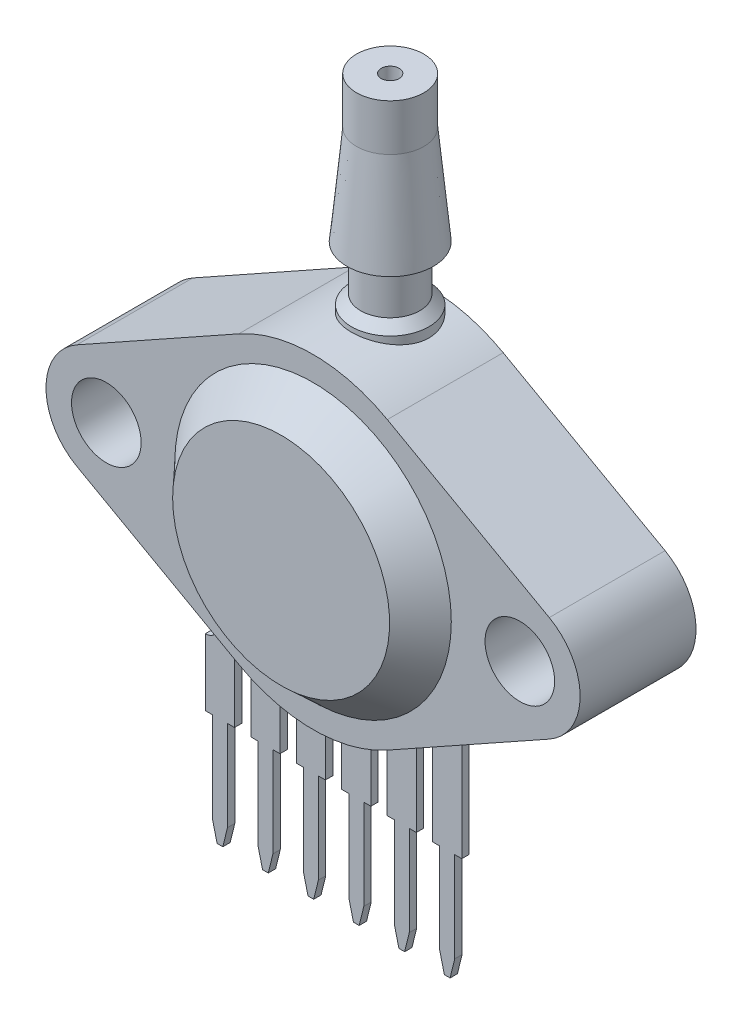
SolidWorks part; units mm, degrees
ref_plane "Front Plane" through (0, 0, 0) normal (0, 0, 1) x (1, 0, 0)
ref_plane "Top Plane" through (0, 0, 0) normal (0, 1, 0) x (1, 0, 0)
ref_plane "Right Plane" through (0, 0, 0) normal (1, 0, 0) x (0, 0, -1)
sketch "Sketch1" plane through (0, 0, 0) normal (0, 0, 1) x (1, 0, 0)
  line L0 (-7.165, -6.4913) -> (-7.165, -7.1728)
  line L1 (-4.625, -8.5934) -> (-4.625, -12.32)
  line L2 (-2.995, -12.32) -> (-2.995, -8.5831)
  line L3 (-7.165, -8.5934) -> (-7.165, -12.32)
  line L4 (-7.165, -12.32) -> (-6.77, -12.32)
  line L5 (-6.77, -12.32) -> (-6.77, -17.3607)
  line L6 (-6.77, -17.3607) -> (-6.5103, -18.42)
  line L7 (-6.5103, -18.42) -> (-6.1897, -18.42)
  line L8 (-6.1897, -18.42) -> (-5.93, -17.3607)
  line L9 (-5.93, -17.3607) -> (-5.93, -12.32)
  line L10 (-5.93, -12.32) -> (-5.535, -12.32)
  line L11 (-5.535, -12.32) -> (-5.535, -8.5831)
  line L12 (-3.39, -12.32) -> (-2.995, -12.32)
  line L13 (-3.39, -17.3607) -> (-3.39, -12.32)
  line L14 (-4.23, -12.32) -> (-4.23, -17.3607)
  line L15 (-4.625, -12.32) -> (-4.23, -12.32)
  line L16 (-3.6497, -18.42) -> (-3.39, -17.3607)
  line L17 (-4.23, -17.3607) -> (-3.9703, -18.42)
  line L18 (-3.9703, -18.42) -> (-3.6497, -18.42)
  line L19 (-2.085, -8.5934) -> (-2.085, -12.32)
  line L20 (-0.455, -12.32) -> (-0.455, -8.5831)
  line L21 (-0.85, -12.32) -> (-0.455, -12.32)
  line L22 (-0.85, -17.3607) -> (-0.85, -12.32)
  line L23 (-1.69, -12.32) -> (-1.69, -17.3607)
  line L24 (-2.085, -12.32) -> (-1.69, -12.32)
  line L25 (-1.1097, -18.42) -> (-0.85, -17.3607)
  line L26 (-1.69, -17.3607) -> (-1.4303, -18.42)
  line L27 (-1.4303, -18.42) -> (-1.1097, -18.42)
  line L28 (0.455, -8.5934) -> (0.455, -12.32)
  line L29 (2.085, -12.32) -> (2.085, -8.5831)
  line L30 (1.69, -12.32) -> (2.085, -12.32)
  line L31 (1.69, -17.3607) -> (1.69, -12.32)
  line L32 (0.85, -12.32) -> (0.85, -17.3607)
  line L33 (0.455, -12.32) -> (0.85, -12.32)
  line L34 (1.4303, -18.42) -> (1.69, -17.3607)
  line L35 (0.85, -17.3607) -> (1.1097, -18.42)
  line L36 (1.1097, -18.42) -> (1.4303, -18.42)
  line L37 (2.995, -8.5934) -> (2.995, -12.32)
  line L38 (4.625, -12.32) -> (4.625, -8.5831)
  line L39 (4.23, -12.32) -> (4.625, -12.32)
  line L40 (4.23, -17.3607) -> (4.23, -12.32)
  line L41 (3.39, -12.32) -> (3.39, -17.3607)
  line L42 (2.995, -12.32) -> (3.39, -12.32)
  line L43 (3.9703, -18.42) -> (4.23, -17.3607)
  line L44 (3.39, -17.3607) -> (3.6497, -18.42)
  line L45 (3.6497, -18.42) -> (3.9703, -18.42)
  line L46 (5.535, -8.5934) -> (5.535, -12.32)
  line L47 (7.165, -12.32) -> (7.165, -8.5831)
  line L48 (6.77, -12.32) -> (7.165, -12.32)
  line L49 (6.77, -17.3607) -> (6.77, -12.32)
  line L50 (5.93, -12.32) -> (5.93, -17.3607)
  line L51 (5.535, -12.32) -> (5.93, -12.32)
  line L52 (6.5103, -18.42) -> (6.77, -17.3607)
  line L53 (5.93, -17.3607) -> (6.1897, -18.42)
  line L54 (6.1897, -18.42) -> (6.5103, -18.42)
  line L55 (-7.165, -8.5934) -> (-4.625, -8.5934) construction
  line L56 (-6.35, -18.42) -> (-6.35, -17.3607) construction
  line L57 (-6.35, -17.3607) -> (-6.77, -17.3607) construction
  line L58 (-5.93, -17.3607) -> (-6.35, -17.3607) construction
  line L59 (0.455, -12.32) -> (0, -12.32) construction
  line L60 (0, -12.32) -> (-0.455, -12.32) construction
  line L61 (-13.1991, 2.9418) -> (-4.1499, 7.9991)
  line L62 (0, 0) -> (-11.555, 0) construction
  line L63 (4.1499, 7.9991) -> (13.1991, 2.9418)
  line L64 (0, 0) -> (0, 0.5736) construction
  line L65 (4.1499, -7.9991) -> (13.1991, -2.9418)
  line L66 (-13.1991, -2.9418) -> (-4.1499, -7.9991)
  arc A0 (-7.165, -7.1728) -> (-7.165, -8.5934) centre (-7.165, -7.8831) cw
  circle A1 centre (-11.555, 0) radius 1.945
  circle A2 centre (11.555, 0) radius 1.945
  arc A3 (-13.1991, 2.9418) -> (-13.1991, -2.9418) centre (-11.555, 0) ccw
  arc A4 (13.1991, -2.9418) -> (13.1991, 2.9418) centre (11.555, 0) ccw
  arc A5 (4.1499, 7.9991) -> (-4.1499, 7.9991) centre (0, 0.5736) ccw
  arc A6 (4.1499, -7.9991) -> (-4.1499, -7.9991) centre (0, -0.5736) cw
  dimension "D6" = 3.89
  dimension "D8" = 23.11
  dimension "D9" = 29.85
  dimension "D1" = 2.54
  dimension "D2" = 1.63
  dimension "D3" = 0.84
  dimension "D4" = 6.1
  dimension "D5" = 18.42
  dimension "D7" = 18.16
sketch "Sketch2" plane through (0, 0, 0) normal (1, 0, 0) x (0, 0, -1)
  line L0 (2.165, -9.08) -> (-2.7529, -9.08)
  line L1 (-4.3102, -9.08) -> (-4.3102, -7.725)
  line L2 (-4.3102, -7.725) -> (-6.095, -6.0632)
  line L3 (-6.095, -6.0632) -> (-6.095, 6.0632)
  line L4 (-6.095, 6.0632) -> (-3.5225, 9.08)
  line L5 (-3.5225, 9.08) -> (-2.165, 9.08)
  line L6 (-2.165, 9.08) -> (-2.165, 9.3423)
  line L7 (-2.165, 9.3423) -> (-1.649, 9.8579)
  line L8 (-1.649, 9.8579) -> (-1.649, 12.3871)
  line L9 (-1.649, 12.3871) -> (2.4115, 12.3871)
  line L10 (2.4115, 12.3871) -> (1.878, 17.9217)
  line L11 (1.878, 17.9217) -> (1.878, 20.5223)
  line L12 (1.878, 20.5223) -> (-1.878, 20.5223)
  line L13 (1.649, 12.3871) -> (-2.4115, 12.3871)
  line L14 (2.165, 9.3423) -> (1.649, 9.8579)
  line L15 (1.649, 9.8579) -> (1.649, 12.3871)
  line L16 (-2.4115, 12.3871) -> (-1.878, 17.9217)
  line L17 (-1.878, 17.9217) -> (-1.878, 20.5223)
  line L18 (-3.1629, -9.08) -> (-4.3102, -9.08)
  line L19 (2.165, 9.3423) -> (2.165, -9.08)
  line L20 (0, 0) -> (0, 20.5223) construction
  line L21 (0, 2.9418) -> (0, -2.9418) construction
  line L22 (-3.1629, -18.6959) -> (-2.7529, -18.6959)
  line L23 (-3.1629, -18.6959) -> (-3.1629, -9.08)
  line L25 (-2.7529, -18.6959) -> (-2.7529, -9.08)
  point P17 (-6.095, 0)
  point P28 (0, -9.08)
  point P30 (0, 9.08)
  dimension "D1" = 6.095
  dimension "D2" = 8.26
  dimension "D3" = 3.7561
  dimension "D4" = 11.18
  dimension "D5" = 18.16
  dimension "D6" = 0.41
sketch "Sketch7" plane through (0, 0, 0) normal (0, 0, 1) x (1, 0, 0)
  line L0 (-5.535, -12.32) -> (-5.535, -8.5831) construction
  line L1 (-5.93, -12.32) -> (-5.535, -12.32) construction
  line L2 (-5.93, -17.3607) -> (-5.93, -12.32) construction
  line L3 (-6.1897, -18.42) -> (-5.93, -17.3607) construction
  line L4 (-6.5103, -18.42) -> (-6.1897, -18.42) construction
  line L5 (-6.77, -17.3607) -> (-6.5103, -18.42) construction
  line L6 (-6.77, -12.32) -> (-6.77, -17.3607) construction
  line L7 (-7.165, -12.32) -> (-6.77, -12.32) construction
  line L8 (-7.165, -8.5934) -> (-7.165, -12.32) construction
  line L9 (-7.165, -6.4913) -> (-7.165, -7.1728) construction
  line L10 (-4.625, -8.5934) -> (-4.625, -12.32) construction
  line L11 (-4.625, -12.32) -> (-4.23, -12.32) construction
  line L12 (-4.23, -12.32) -> (-4.23, -17.3607) construction
  line L13 (-4.23, -17.3607) -> (-3.9703, -18.42) construction
  line L14 (-3.9703, -18.42) -> (-3.6497, -18.42) construction
  line L15 (-3.6497, -18.42) -> (-3.39, -17.3607) construction
  line L16 (-3.39, -17.3607) -> (-3.39, -12.32) construction
  line L17 (-3.39, -12.32) -> (-2.995, -12.32) construction
  line L18 (-2.995, -12.32) -> (-2.995, -8.5831) construction
  line L19 (-0.455, -12.32) -> (-0.455, -8.5831) construction
  line L20 (-0.85, -12.32) -> (-0.455, -12.32) construction
  line L21 (-0.85, -17.3607) -> (-0.85, -12.32) construction
  line L22 (-1.1097, -18.42) -> (-0.85, -17.3607) construction
  line L23 (-1.4303, -18.42) -> (-1.1097, -18.42) construction
  line L24 (-1.69, -17.3607) -> (-1.4303, -18.42) construction
  line L25 (-1.69, -12.32) -> (-1.69, -17.3607) construction
  line L26 (-2.085, -12.32) -> (-1.69, -12.32) construction
  line L27 (-2.085, -8.5934) -> (-2.085, -12.32) construction
  line L28 (4.625, -12.32) -> (4.625, -8.5831) construction
  line L29 (4.23, -12.32) -> (4.625, -12.32) construction
  line L30 (4.23, -17.3607) -> (4.23, -12.32) construction
  line L31 (3.9703, -18.42) -> (4.23, -17.3607) construction
  line L32 (3.6497, -18.42) -> (3.9703, -18.42) construction
  line L33 (3.39, -17.3607) -> (3.6497, -18.42) construction
  line L34 (3.39, -12.32) -> (3.39, -17.3607) construction
  line L35 (2.995, -12.32) -> (3.39, -12.32) construction
  line L36 (2.995, -8.5934) -> (2.995, -12.32) construction
  line L37 (0.455, -8.5934) -> (0.455, -12.32) construction
  line L38 (0.455, -12.32) -> (0.85, -12.32) construction
  line L39 (0.85, -12.32) -> (0.85, -17.3607) construction
  line L40 (0.85, -17.3607) -> (1.1097, -18.42) construction
  line L41 (1.1097, -18.42) -> (1.4303, -18.42) construction
  line L42 (1.4303, -18.42) -> (1.69, -17.3607) construction
  line L43 (1.69, -17.3607) -> (1.69, -12.32) construction
  line L44 (1.69, -12.32) -> (2.085, -12.32) construction
  line L45 (2.085, -12.32) -> (2.085, -8.5831) construction
  line L46 (5.535, -8.5934) -> (5.535, -12.32) construction
  line L47 (5.535, -12.32) -> (5.93, -12.32) construction
  line L48 (5.93, -12.32) -> (5.93, -17.3607) construction
  line L49 (5.93, -17.3607) -> (6.1897, -18.42) construction
  line L50 (6.1897, -18.42) -> (6.5103, -18.42) construction
  line L51 (6.5103, -18.42) -> (6.77, -17.3607) construction
  line L52 (6.77, -17.3607) -> (6.77, -12.32) construction
  line L53 (6.77, -12.32) -> (7.165, -12.32) construction
  line L54 (7.165, -12.32) -> (7.165, -8.5831) construction
  line L55 (-5.535, -12.32) -> (-5.535, -7.225)
  line L56 (-5.93, -12.32) -> (-5.535, -12.32)
  line L57 (-5.93, -17.3607) -> (-5.93, -12.32)
  line L58 (-6.1897, -18.42) -> (-5.93, -17.3607)
  line L59 (-6.5103, -18.42) -> (-6.1897, -18.42)
  line L60 (-6.77, -17.3607) -> (-6.5103, -18.42)
  line L61 (-6.77, -12.32) -> (-6.77, -17.3607)
  line L62 (-7.165, -12.32) -> (-6.77, -12.32)
  line L63 (-7.165, -8.5934) -> (-7.165, -12.32)
  line L64 (-7.165, -6.314) -> (-7.165, -7.1728)
  line L65 (-4.625, -7.7335) -> (-4.625, -12.32)
  line L66 (-4.625, -12.32) -> (-4.23, -12.32)
  line L67 (-4.23, -12.32) -> (-4.23, -17.3607)
  line L68 (-4.23, -17.3607) -> (-3.9703, -18.42)
  line L69 (-3.9703, -18.42) -> (-3.6497, -18.42)
  line L70 (-3.6497, -18.42) -> (-3.39, -17.3607)
  line L71 (-3.39, -17.3607) -> (-3.39, -12.32)
  line L72 (-3.39, -12.32) -> (-2.995, -12.32)
  line L73 (-2.995, -12.32) -> (-2.995, -8.5353)
  line L74 (-0.455, -12.32) -> (-0.455, -9.0678)
  line L75 (-0.85, -12.32) -> (-0.455, -12.32)
  line L76 (-0.85, -17.3607) -> (-0.85, -12.32)
  line L77 (-1.1097, -18.42) -> (-0.85, -17.3607)
  line L78 (-1.4303, -18.42) -> (-1.1097, -18.42)
  line L79 (-1.69, -17.3607) -> (-1.4303, -18.42)
  line L80 (-1.69, -12.32) -> (-1.69, -17.3607)
  line L81 (-2.085, -12.32) -> (-1.69, -12.32)
  line L82 (-2.085, -8.8205) -> (-2.085, -12.32)
  line L83 (4.625, -12.32) -> (4.625, -7.7335)
  line L84 (4.23, -12.32) -> (4.625, -12.32)
  line L85 (4.23, -17.3607) -> (4.23, -12.32)
  line L86 (3.9703, -18.42) -> (4.23, -17.3607)
  line L87 (3.6497, -18.42) -> (3.9703, -18.42)
  line L88 (3.39, -17.3607) -> (3.6497, -18.42)
  line L89 (3.39, -12.32) -> (3.39, -17.3607)
  line L90 (2.995, -12.32) -> (3.39, -12.32)
  line L91 (2.995, -8.5353) -> (2.995, -12.32)
  line L92 (0.455, -9.0678) -> (0.455, -12.32)
  line L93 (0.455, -12.32) -> (0.85, -12.32)
  line L94 (0.85, -12.32) -> (0.85, -17.3607)
  line L95 (0.85, -17.3607) -> (1.1097, -18.42)
  line L96 (1.1097, -18.42) -> (1.4303, -18.42)
  line L97 (1.4303, -18.42) -> (1.69, -17.3607)
  line L98 (1.69, -17.3607) -> (1.69, -12.32)
  line L99 (1.69, -12.32) -> (2.085, -12.32)
  line L100 (2.085, -12.32) -> (2.085, -8.8205)
  line L101 (5.535, -7.225) -> (5.535, -12.32)
  line L102 (5.535, -12.32) -> (5.93, -12.32)
  line L103 (5.93, -12.32) -> (5.93, -17.3607)
  line L104 (5.93, -17.3607) -> (6.1897, -18.42)
  line L105 (6.1897, -18.42) -> (6.5103, -18.42)
  line L106 (6.5103, -18.42) -> (6.77, -17.3607)
  line L107 (6.77, -17.3607) -> (6.77, -12.32)
  line L108 (6.77, -12.32) -> (7.165, -12.32)
  line L109 (7.165, -12.32) -> (7.165, -6.314)
  line L110 (5.535, -7.225) -> (7.165, -6.314)
  line L111 (-4.625, -7.7335) -> (-4.1499, -7.9991)
  line L114 (4.1499, -7.9991) -> (13.1991, -2.9418)
  line L115 (-13.1991, -2.9418) -> (-4.1499, -7.9991)
  line L116 (-4.1499, 7.9991) -> (-13.1991, 2.9418)
  line L117 (13.1991, 2.9418) -> (4.1499, 7.9991)
  line L118 (4.1499, -7.9991) -> (4.625, -7.7335)
  line L119 (-7.165, -6.314) -> (-5.535, -7.225)
  arc A0 (-7.165, -8.5934) -> (-7.165, -7.1728) centre (-7.165, -7.8831) ccw construction
  arc A1 (-7.165, -8.5934) -> (-7.165, -7.1728) centre (-7.165, -7.8831) ccw
  arc A2 (2.995, -8.5353) -> (4.1499, -7.9991) centre (0, -0.5736) ccw
  arc A3 (0.455, -9.0678) -> (2.085, -8.8205) centre (0, -0.5736) ccw
  arc A4 (-2.085, -8.8205) -> (-0.455, -9.0678) centre (0, -0.5736) ccw
  arc A10 (13.1991, -2.9418) -> (13.1991, 2.9418) centre (11.555, 0) ccw
  arc A11 (-4.1499, -7.9991) -> (4.1499, -7.9991) centre (0, -0.5736) ccw
  arc A12 (-13.1991, 2.9418) -> (-13.1991, -2.9418) centre (-11.555, 0) ccw
  arc A13 (4.1499, 7.9991) -> (-4.1499, 7.9991) centre (0, 0.5736) ccw
  arc A15 (-4.1499, -7.9991) -> (-2.995, -8.5353) centre (0, -0.5736) ccw
  dimension "D3" = 0
sketch "Sketch4" plane through (0, 0, 0) normal (1, 0, 0) x (0, 0, -1)
  line L0 (-2.7529, -18.6959) -> (-2.7529, -9.08) construction
  line L4 (-3.1629, -18.6959) -> (-2.7529, -18.6959) construction
  line L5 (-3.1629, -18.6959) -> (-3.1629, -9.08) construction
  line L47 (-3.5225, 9.08) -> (-2.165, 9.08) construction
  line L95 (-3.1629, -18.6959) -> (-2.7529, -18.6959)
  line L96 (-2.7529, -18.6959) -> (-2.7529, 9.08)
  line L111 (-3.1629, 9.08) -> (-2.7529, 9.08)
  line L117 (-3.1629, -18.6959) -> (-3.1629, 9.08)
extrude "Extrude6" add sketch "Sketch7" along normal up to vertex (3.1629 mm away) up to point (0, -18.6959, 3.1629)
extrude "Extrude7" cut sketch "Sketch4" against normal through all and the other way through all flip side to cut
sketch "Sketch3" plane through (0, 0, 0) normal (0, 0, 1) x (1, 0, 0)
  line L55 (4.1499, -7.9991) -> (13.1991, -2.9418) construction
  line L56 (-13.1991, -2.9418) -> (-4.1499, -7.9991) construction
  line L57 (4.1499, -7.9991) -> (13.1991, -2.9418)
  line L58 (-13.1991, -2.9418) -> (-4.1499, -7.9991)
  line L114 (4.1499, -7.9991) -> (13.1991, -2.9418)
  line L115 (-13.1991, -2.9418) -> (-4.1499, -7.9991)
  line L116 (-4.1499, 7.9991) -> (-13.1991, 2.9418)
  line L117 (13.1991, 2.9418) -> (4.1499, 7.9991)
  line L120 (-4.1499, 7.9991) -> (-13.1991, 2.9418)
  line L121 (13.1991, 2.9418) -> (4.1499, 7.9991)
  arc A1 (-4.1499, -7.9991) -> (4.1499, -7.9991) centre (0, -0.5736) ccw construction
  arc A2 (-4.1499, -7.9991) -> (4.1499, -7.9991) centre (0, -0.5736) ccw
  circle A3 centre (11.555, 0) radius 1.945
  circle A4 centre (11.555, 0) radius 1.945
  circle A5 centre (-11.555, 0) radius 1.945
  circle A6 centre (-11.555, 0) radius 1.945
  arc A10 (13.1991, -2.9418) -> (13.1991, 2.9418) centre (11.555, 0) ccw
  arc A11 (-4.1499, -7.9991) -> (4.1499, -7.9991) centre (0, -0.5736) ccw
  arc A12 (-13.1991, 2.9418) -> (-13.1991, -2.9418) centre (-11.555, 0) ccw
  arc A13 (4.1499, 7.9991) -> (-4.1499, 7.9991) centre (0, 0.5736) ccw
  arc A14 (13.1991, -2.9418) -> (13.1991, 2.9418) centre (11.555, 0) ccw
  arc A16 (-13.1991, 2.9418) -> (-13.1991, -2.9418) centre (-11.555, 0) ccw
  arc A17 (4.1499, 7.9991) -> (-4.1499, 7.9991) centre (0, 0.5736) ccw
  dimension "D1" = 0
  dimension "D2" = 0
  dimension "D3" = 0
extrude "Extrude1" add sketch "Sketch3" along normal up to vertex (6.095 mm away) and the other way up to vertex (2.165 mm away) up to point (0, 6.0632, 6.095) other way up to point (0, 9.3423, -2.165)
sketch "Sketch5" plane through (0, 0, 0) normal (1, 0, 0) x (0, 0, -1)
  line L4 (-4.3102, -9.08) -> (-4.3102, -7.725) construction
  line L5 (-4.3102, -7.725) -> (-6.095, -6.0632) construction
  line L23 (-4.3102, -16.0632) -> (-4.3102, -7.725)
  line L24 (-4.3102, -7.725) -> (-6.095, -6.0632)
  line L25 (-4.3102, -16.0632) -> (-6.095, -16.0632)
  line L26 (-6.095, -16.0632) -> (-6.095, -6.0632)
  line L27 (0, 0) -> (-6.095, 0) construction
  dimension "D1" = 10
revolve "Cut-Revolve1" cut sketch "Sketch5" angle 360 about L27
sketch "Sketch8" plane through (0, 0, 0) normal (1, 0, 0) x (0, 0, -1)
  line L9 (-2.165, 9.08) -> (-2.165, 9.3423) construction
  line L10 (-2.165, 9.3423) -> (-1.649, 9.8579) construction
  line L11 (-1.649, 9.8579) -> (-1.649, 12.3871) construction
  line L15 (1.878, 20.5223) -> (-1.878, 20.5223) construction
  line L16 (-1.878, 17.9217) -> (-1.878, 20.5223) construction
  line L17 (-2.4115, 12.3871) -> (-1.878, 17.9217) construction
  line L18 (1.649, 12.3871) -> (-2.4115, 12.3871) construction
  line L23 (0, 0) -> (0, 20.5223)
  line L25 (-2.165, 0) -> (0, 0)
  line L26 (0, 20.5223) -> (0, 22.4003) construction
  line L35 (-2.165, 0) -> (-2.165, 9.3423)
  line L36 (-2.165, 9.3423) -> (-1.649, 9.8579)
  line L37 (-1.649, 9.8579) -> (-1.649, 12.3871)
  line L41 (0, 20.5223) -> (-1.878, 20.5223)
  line L42 (-1.878, 17.9217) -> (-1.878, 20.5223)
  line L43 (-2.4115, 12.3871) -> (-1.878, 17.9217)
  line L44 (-1.649, 12.3871) -> (-2.4115, 12.3871)
revolve "Revolve1" add sketch "Sketch8" angle 360 about L26
hole_wizard "Ø1.0 (1) Diameter Hole1" positions "3DSketch1" profile "Sketch9" hole size "Ø1.0" standard "Ansi Metric"
sketch3d "3DSketch1"
  line L0 (0, 20.5223, 0) -> (0, 17.9217, 0) construction
  point P0 (0, 20.5223, 0)
sketch "Sketch9" plane through (0, 20.5223, 0) normal (1, 0, 0) x (0, 0, 1)
  line L0 (0, 0) -> (0, 14.2704)
  line L1 (0, 14.2704) -> (0.5, 13.97)
  line L2 (0.5, 13.97) -> (0.5, 0)
  line L5 (0.5, 0) -> (0, 0)
  line L10 (0, 14.2704) -> (-0.5, 13.97) construction
  line L11 (0, -6.35) -> (0, 107.95) construction
  dimension "Hole Dia." = 1
  dimension "Hole Depth" = 13.97
  dimension "Drill Angle" = 118
